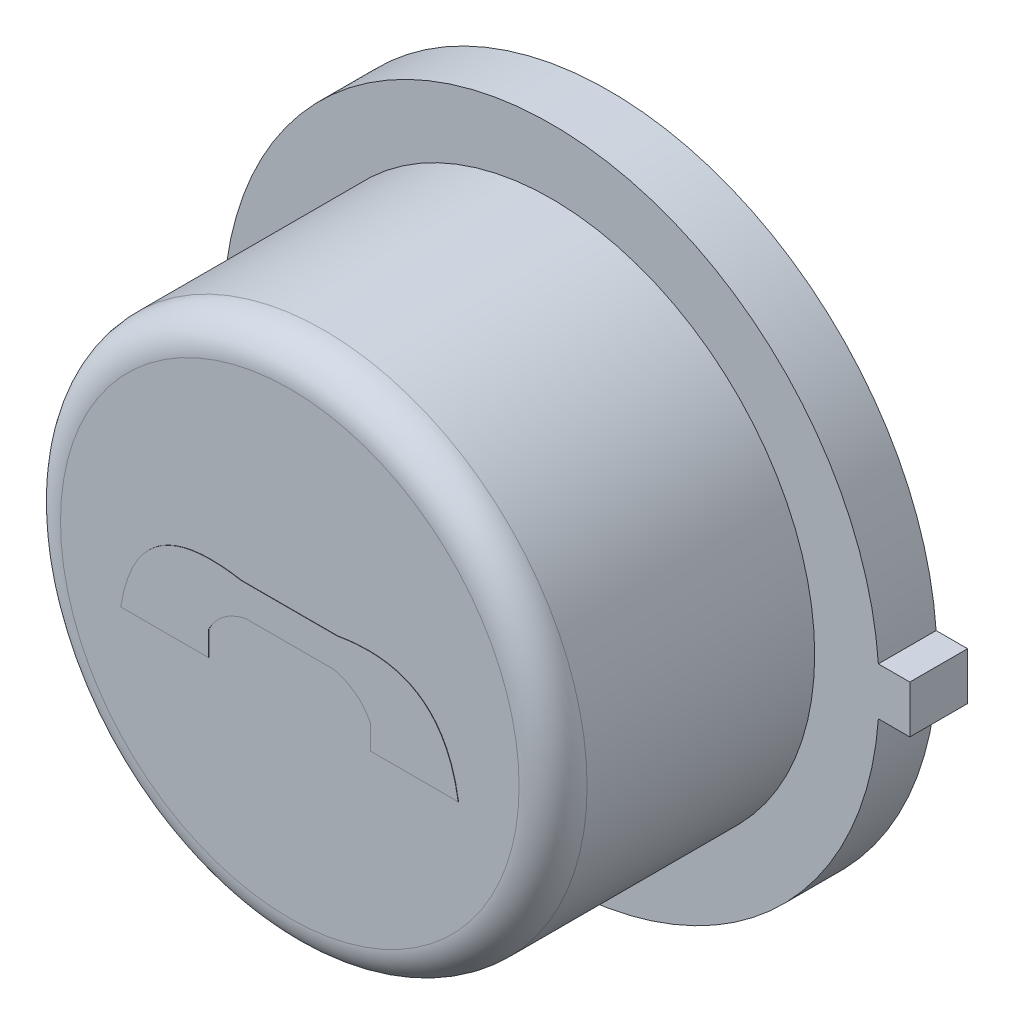
SolidWorks part; units mm, degrees
ref_plane "Front Plane" through (0, 0, 0) normal (0, 0, 1) x (1, 0, 0)
ref_plane "Top Plane" through (0, 0, 0) normal (0, 1, 0) x (1, 0, 0)
ref_plane "Right Plane" through (0, 0, 0) normal (1, 0, 0) x (0, 0, -1)
sketch "Sketch1" plane through (0, 0, 0) normal (0, 0, 1) x (1, 0, 0)
  line L1 (2.4511, 0.1778) -> (2.6797, 0.1778)
  line L3 (2.4511, -0.1778) -> (2.6797, -0.1778)
  line L4 (2.6797, 0.1778) -> (2.6797, -0.1778)
  line L5 (2.4511, 0.1778) -> (2.4444, 0.1778)
  line L6 (2.4511, -0.1778) -> (2.4446, -0.1778)
  arc A0 (2.4446, 0.1778) -> (2.4446, -0.1778) centre (0, 0) ccw
  dimension "D1" = 4.9022
  dimension "D2" = 0.3556
  dimension "D3" = 0.2286
extrude "Boss-Extrude1" add sketch "Sketch1" along normal blind 0.4318 contours A0 L6 L3 L4 L1 L5 region at (0.0111, 0, 0)
sketch "Sketch2" plane through (0, 0, 0.4318) normal (0, 0, 1) x (1, 0, 0)
  circle A0 centre (0, 0) radius 1.9685
  dimension "D1" = 3.937
extrude "Boss-Extrude2" add sketch "Sketch2" along normal blind 1.9558
sketch "Sketch3" plane through (0, 0, 0) normal (0, 0, -1) x (-1, 0, 0)
  circle A0 centre (0, 0) radius 1.7576
extrude "Boss-Extrude3" add sketch "Sketch3" along normal blind 0.0025
fillet "Fillet1" radius 0.254 1 edges at (1.9685, 0, 2.3876)
sketch "Sketch4" plane through (0, 0, 2.3876) normal (0, 0, 1) x (1, 0, 0)
  line L0 (0, 1.7145) -> (0, -1.7145) construction
  line L1 (-1.2617, -0.3273) -> (-0.6059, -0.3273)
  line L2 (-0.6059, -0.3273) -> (-0.6059, -0.1457)
  line L3 (-0.3288, 0.0646) -> (0.3288, 0.0646)
  line L4 (-0.3599, 0.2939) -> (0.3599, 0.2939)
  line L5 (1.2617, -0.3273) -> (0.6059, -0.3273)
  line L6 (0.6059, -0.3273) -> (0.6059, -0.1457)
  circle A1 centre (0, 0) radius 1.7145 construction
  spline S0 degree 2 poles (-1.2617, -0.3273) (-1.1425, 0.434) (-0.3599, 0.2939) knots 0 0 0 1 1 1
  spline S1 degree 2 poles (-0.6059, -0.1457) (-0.5204, 0.0209) (-0.3288, 0.0646) knots 0 0 0 1 1 1
  spline S2 degree 2 poles (1.2617, -0.3273) (1.1425, 0.434) (0.3599, 0.2939) knots 0 0 0 1 1 1
  spline S3 degree 2 poles (0.6059, -0.1457) (0.5204, 0.0209) (0.3288, 0.0646) knots 0 0 0 1 1 1
  point P15 (0, 0.0646)
  point P16 (0, 0.2939)
extrude "Boss-Extrude6" add sketch "Sketch4" along normal blind 0.0025 contours S3 L6 L5 S2 L4 S0 L1 L2 S1 L3 region at (-0.9562, 0.1911, 2.3876)
